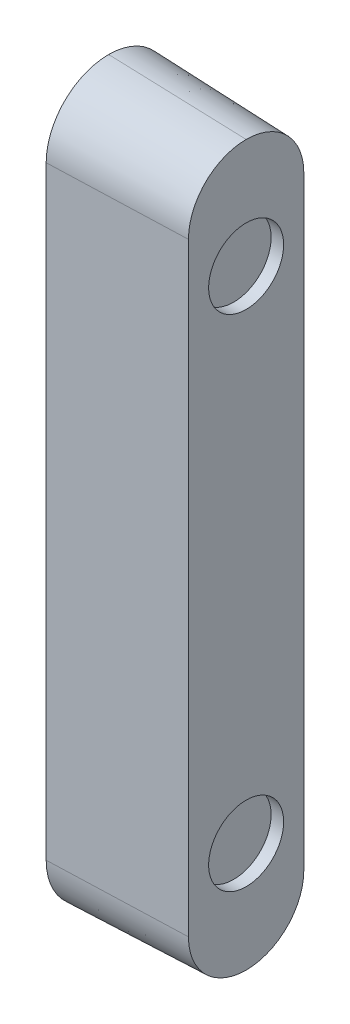
SolidWorks part; units mm, degrees
material "Stainless Steel (ferritic)"
ref_plane "Front Plane" through (0, 0, 0) normal (0, 0, 1) x (1, 0, 0)
ref_plane "Top Plane" through (0, 0, 0) normal (0, 1, 0) x (1, 0, 0)
ref_plane "Right Plane" through (0, 0, 0) normal (1, 0, 0) x (0, 0, -1)
sketch "Sketch1" plane through (0, 0, 0) normal (1, 0, 0) x (0, 0, -1)
  line L1 (-15, -87.5) -> (15, -87.5)
  line L2 (-15, -87.5) -> (-15, 87.5)
  line L3 (-15, 87.5) -> (15, 87.5)
  line L4 (15, -87.5) -> (15, 87.5)
  line L5 (-15, -87.5) -> (15, 87.5) construction
  line L6 (-15, 87.5) -> (15, -87.5) construction
  point P0 (0, 0)
  dimension "D1" = 30
  dimension "D2" = 175
extrude "Boss-Extrude1" add sketch "Sketch1" along normal blind 16.5 and the other way blind 16.5
sketch "Sketch2" plane through (16.5, 0, 0) normal (1, 0, 0) x (0, 0, -1)
  line L0 (0, -60) -> (0, 60) construction
  circle A2 centre (0, -60) radius 9
  circle A3 centre (0, 60) radius 9
  dimension "D2" = 18
  dimension "D3" = 18
  dimension "D1" = 120
extrude "Cut-Extrude1" cut sketch "Sketch2" against normal blind 3
fillet "Fillet1" radius 15 4 edges at (0, 87.5, -15) (0, 87.5, 15) (0, -87.5, -15) (0, -87.5, 15)
sketch "Sketch3" plane through (0, 0, -15) normal (0, 0, -1) x (-1, 0, 0)
  line L0 (16.5, -72.5) -> (16.5, 72.5) construction
  line L1 (0, 0) -> (-0.6, 0) construction
  circle A0 centre (-0.6, 0) radius 4
  dimension "D2" = 8
  dimension "D1" = 17.1
extrude "Cut-Extrude2" cut sketch "Sketch3" against normal blind 4
draft "Draft1" type of draft neutral plane draft angle 2 faces to draft 6 face at (0, -81.5533, -9.0533) face at (-3.4, 0, -15) face at (0, 81.5533, -9.0533) face at (0, 81.5533, 9.0533) face at (0, 0, 15) face at (0, -81.5533, 9.0533) neutral plane through (-16.5, 0, 0) neutral plane normal (-1, 0, 0) reverse direction yes parameters "D1"=2
sketch3d "URDF Reference"
  line L0 (0, 0, 0) -> (10, 0, 0) construction
  line L1 (0, 0, 0) -> (0, 0, -10) construction
  point P0 (0, 0, 0)
  point P1 (0, 0, 0)
